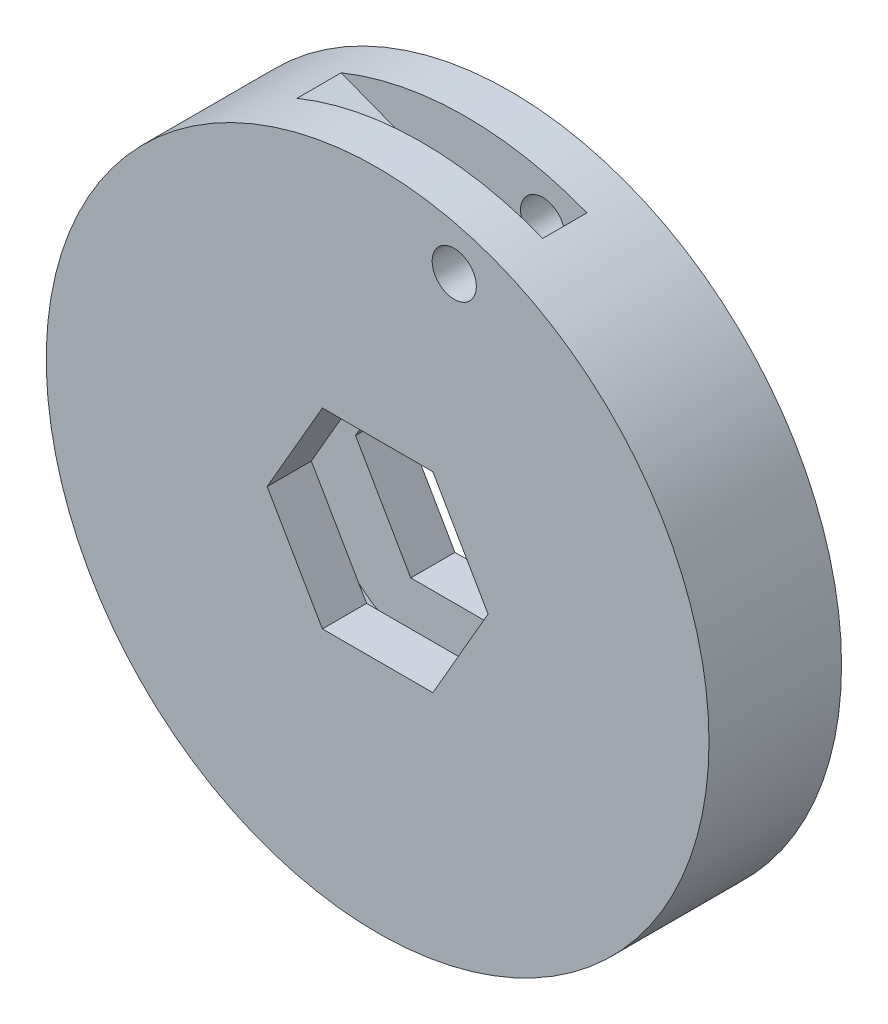
SolidWorks part; units mm, degrees
ref_plane "前视基准面" through (0, 0, 0) normal (0, 0, 1) x (1, 0, 0)
ref_plane "上视基准面" through (0, 0, 0) normal (0, 1, 0) x (1, 0, 0)
ref_plane "右视基准面" through (0, 0, 0) normal (1, 0, 0) x (0, 0, -1)
sketch "草图1" plane through (0, 0, 0) normal (0, 0, 1) x (1, 0, 0)
  circle A0 centre (0, 0) radius 15
  dimension "D1" = 30
extrude "凸台-拉伸1" add sketch "草图1" along normal blind 6
sketch "草图2" plane through (0, 0, 6) normal (0, 0, 1) x (1, 0, 0)
  line L0 (-5.6496, 13.8954) -> (2.7497, 10.6623)
  line L1 (5.4681, 12.522) -> (5.4731, 13.9659)
  circle A0 centre (0, 0) radius 15 construction
  arc A1 (2.7497, 10.6623) -> (5.4681, 12.522) centre (3.4681, 12.5288) ccw
  arc A3 (5.4731, 13.9659) -> (-5.6496, 13.8954) centre (0, 0) ccw
  dimension "D1" = 4
  dimension "D2" = 9
extrude "切除-拉伸1" cut sketch "草图2" against normal through all
sketch "草图5" plane through (0, 0, 6) normal (0, 0, 1) x (1, 0, 0)
  circle A0 centre (0, 0) radius 7.5
  dimension "D1" = 15
extrude "切除-拉伸2" cut sketch "草图5" against normal through all
sketch "草图6" plane through (0, 0, 6) normal (0, 0, 1) x (1, 0, 0)
  circle A0 centre (0, 0) radius 15
  arc A1 (-5.6496, 13.8954) -> (5.4731, 13.9659) centre (0, 0) ccw construction
extrude "凸台-拉伸4" add sketch "草图6" against normal blind 2
sketch "草图7" plane through (0, 0, 0) normal (0, 0, -1) x (-1, 0, 0)
  circle A0 centre (0, 0) radius 15
  arc A1 (-5.4731, 13.9659) -> (5.6496, 13.8954) centre (0, 0) ccw construction
extrude "凸台-拉伸5" add sketch "草图7" against normal blind 2
sketch "草图8" plane through (0, 0, 2) normal (0, 0, 1) x (1, 0, 0)
  circle A1 centre (3.4681, 12.5725) radius 1
  point P3 (3.4681, 12.5725)
  dimension "D1" = 2
extrude "切除-拉伸3" cut sketch "草图8" against normal through all both and the other way through all
sketch "草图9" plane through (0, 0, 6) normal (0, 0, 1) x (1, 0, 0)
  line L1 (2.5, -4.3301) -> (5, 0)
  line L2 (5, 0) -> (2.5, 4.3301)
  line L3 (2.5, 4.3301) -> (-2.5, 4.3301)
  line L4 (-2.5, 4.3301) -> (-5, 0)
  line L5 (-5, 0) -> (-2.5, -4.3301)
  line L6 (-2.5, -4.3301) -> (2.5, -4.3301)
  circle A1 centre (0, 0) radius 5 construction
  dimension "D1" = 10
extrude "切除-拉伸4" cut sketch "草图9" against normal through all
